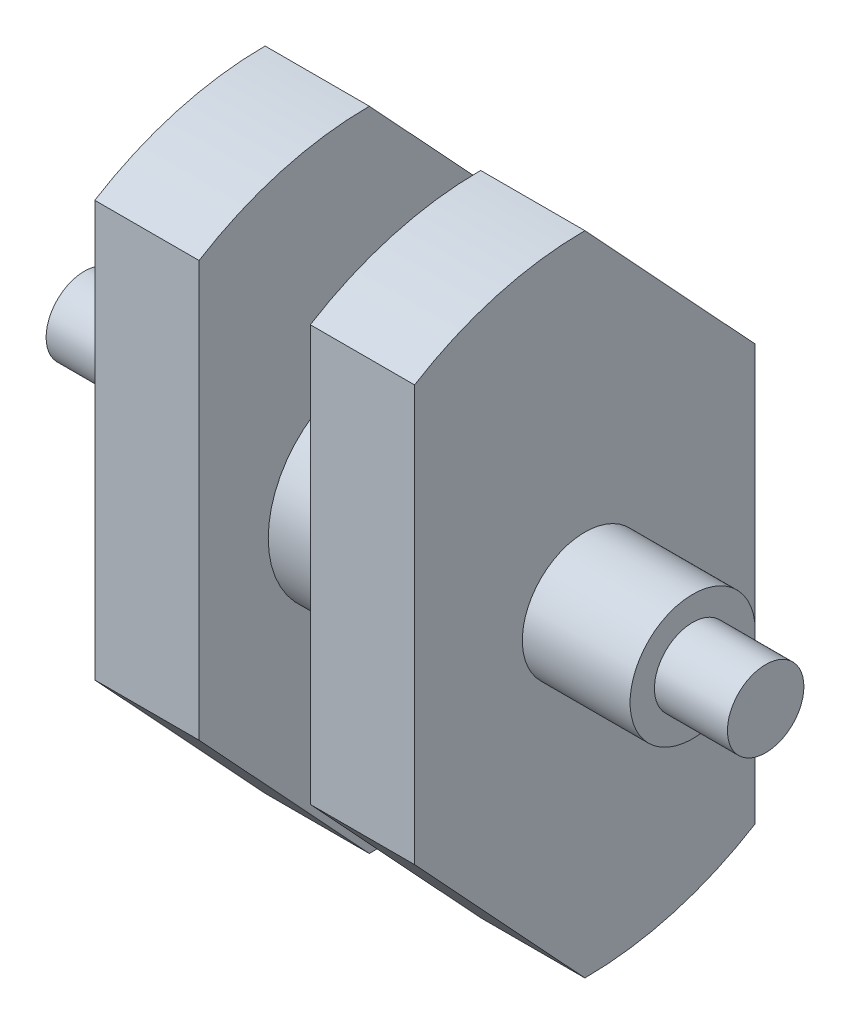
SolidWorks part; units mm, degrees
material "AISI 4340 Aço, normalizado"
ref_plane "Plano frontal" through (0, 0, 0) normal (0, 0, 1) x (1, 0, 0)
ref_plane "Plano superior" through (0, 0, 0) normal (0, 1, 0) x (1, 0, 0)
ref_plane "Plano direito" through (0, 0, 0) normal (1, 0, 0) x (0, 0, -1)
sketch "Esboço1" plane through (0, 0, 0) normal (1, 0, 0) x (0, 0, -1)
  circle A0 centre (0, 0) radius 46.55
  dimension "D1" = 93.1
extrude "Ressalto-extrusão1" add sketch "Esboço1" along normal mid plane 98
sketch "Esboço2" plane through (0, 0, 0) normal (1, 0, 0) x (0, 0, -1)
  line L0 (0, -1000) -> (0, 49000) construction
  line L1 (-1000, 0) -> (49000, 0) construction
  line L2 (24.5, 60.3021) -> (24.5, -60.3021)
  line L3 (-24.5, 60.3021) -> (-24.5, -60.3021)
  line L4 (0, 46.55) -> (24.5, 20.1729)
  line L6 (0, -46.55) -> (-24.5, -20.1729)
  circle A0 centre (0, 0) radius 46.55 construction
  circle A2 centre (0, 0) radius 46.55
  point P8 (24.5, 0)
  dimension "D1" = 24.5
extrude "Corte-extrusão2" cut sketch "Esboço2" against normal through all both and the other way through all contours L3 A2 | L3 A2 L6 | L2 A2 | L2 A2 L4 region at (0, 0, -33.5278) region at (0, 36.374, -15.894) region at (0, 0, 33.5278) region at (0, -36.374, 15.894)
sketch "Esboço3" plane through (0, 0, 0) normal (1, 0, 0) x (0, 0, -1)
  circle A0 centre (0, 0) radius 9
extrude "Corte-extrusão10" cut sketch "Esboço3" along normal blind 26 from surface flip side to cut starting at face at (-49, 0, 0)
sketch "Esboço6" plane through (0, 0, 0) normal (1, 0, 0) x (0, 0, -1)
  circle A0 centre (0, 0) radius 9
extrude "Corte-extrusão11" cut sketch "Esboço6" against normal blind 26 from surface flip side to cut starting at face at (49, 0, 0)
sketch "Esboço7" plane through (49, 0, 0) normal (1, 0, 0) x (0, 0, -1)
  circle A1 centre (0, 0) radius 5.5
extrude "Corte-extrusão12" cut sketch "Esboço7" against normal blind 10.5 from surface flip side to cut starting at face at (49, 0, -9)
sketch "Esboço8" plane through (-49, 0, 0) normal (-1, 0, 0) x (0, 0, 1)
  circle A0 centre (0, 0) radius 5.5
extrude "Corte-extrusão13" cut sketch "Esboço8" against normal blind 10.5 flip side to cut
sketch "Esboço9" plane through (0, 0, 0) normal (0, 0, 1) x (1, 0, 0)
  line L0 (-8, 39.581) -> (-8, 30.0139) construction
  line L1 (-23, 39.581) -> (23, 39.581) construction
  line L2 (-23, 39.581) -> (-23, -20.1729) construction
  line L3 (0, -1000) -> (0, 49000) construction
  line L4 (8, 39.581) -> (8, 30.0139) construction
  line L5 (-1000, 0) -> (49000, 0) construction
  line L6 (-8, 14.55) -> (8, 14.55) construction
  line L7 (-23, 46.55) -> (23, 46.55) construction
  line L8 (-8, 14.55) -> (-8, 51.4116)
  line L9 (-8, 51.4116) -> (8, 51.4116)
  line L10 (8, 51.4116) -> (8, 14.55)
  line L11 (8, 14.55) -> (-8, 14.55)
  point P16 (0, 14.55)
  dimension "D1" = 15
  dimension "D2" = 32
revolve "Corte-Revolução1" cut sketch "Esboço9" angle 360 about L5
